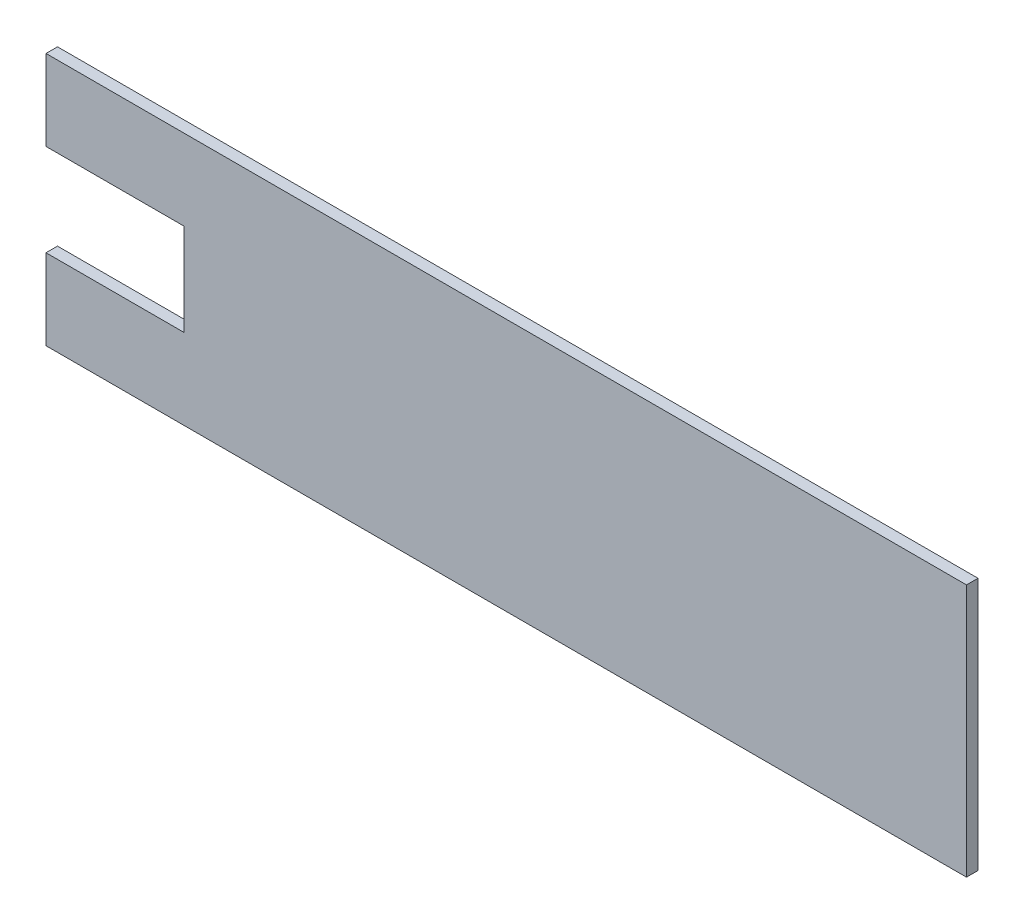
SolidWorks part; units mm, degrees
ref_plane "Front Plane" through (0, 0, 0) normal (0, 0, 1) x (1, 0, 0)
ref_plane "Top Plane" through (0, 0, 0) normal (0, 1, 0) x (1, 0, 0)
ref_plane "Right Plane" through (0, 0, 0) normal (1, 0, 0) x (0, 0, -1)
sketch "Sketch1" plane through (0, 0, 0) normal (0, 0, 1) x (1, 0, 0)
  line L1 (0, 0) -> (254, 0)
  line L2 (0, 0) -> (0, 69.85)
  line L3 (0, 69.85) -> (254, 69.85)
  line L4 (254, 0) -> (254, 69.85)
  dimension "D1" = 69.85
  dimension "D2" = 254
extrude "Boss-Extrude1" add sketch "Sketch1" along normal blind 3.175
sketch "Sketch2" plane through (0, 0, 3.175) normal (0, 0, 1) x (1, 0, 0)
  line L0 (0, 69.85) -> (0, 0) construction
  line L1 (0, 47.625) -> (38.1, 47.625)
  line L2 (0, 47.625) -> (0, 22.225)
  line L3 (0, 22.225) -> (38.1, 22.225)
  line L4 (38.1, 47.625) -> (38.1, 22.225)
  line L5 (254, 0) -> (254, 69.85) construction
  point P6 (38.1, 34.925)
  point P7 (254, 34.925)
  dimension "D1" = 25.4
  dimension "D2" = 38.1
extrude "Cut-Extrude1" cut sketch "Sketch2" against normal through all
